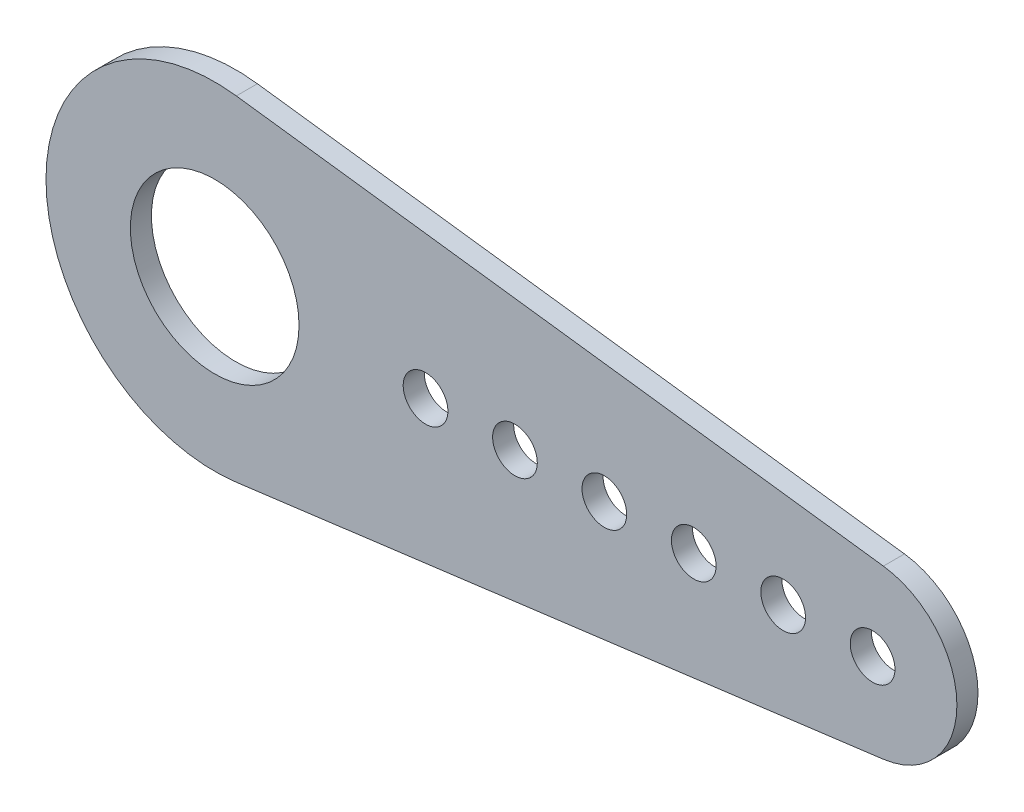
SolidWorks part; units mm, degrees
material "Custom Plastic"
ref_plane "X-Y Datum" through (0, 0, 0) normal (0, 0, 1) x (1, 0, 0)
ref_plane "X-Z Datum" through (0, 0, 0) normal (0, 1, 0) x (1, 0, 0)
ref_plane "Y-Z Datum" through (0, 0, 0) normal (1, 0, 0) x (0, 0, -1)
sketch "Flat sketch" plane through (0, 0, 0) normal (0, 0, 1) x (1, 0, 0)
  line L0 (-12.7, 0) -> (99.06, 0) construction
  line L1 (99.06, 0) -> (85.598, 0) construction
  line L2 (3.2564, 25.1904) -> (100.6882, 12.5952)
  line L3 (3.2564, -25.1904) -> (100.6882, -12.5952)
  line L4 (100.6882, 12.5952) -> (100.6882, -12.5952) construction
  circle A0 centre (0, 0) radius 12.7
  circle A1 centre (0, 0) radius 25.4
  circle A2 centre (99.06, 0) radius 3.3655
  circle A3 centre (85.598, 0) radius 3.3655
  circle A4 centre (72.136, 0) radius 3.3655
  circle A5 centre (58.674, 0) radius 3.3655
  circle A6 centre (45.212, 0) radius 3.3655
  circle A7 centre (31.75, 0) radius 3.3655
  circle A8 centre (99.06, 0) radius 12.7
  point P5 (12.7, 0)
  point P9 (25.4, 0)
  dimension "D1" = 25.4
  dimension "D2" = 50.8
  dimension "D3" = 6.731
  dimension "D7" = 25.4
  dimension "D5" = 13.462
  dimension "D6" = 6.35
  dimension "D4" = 6
extrude "Extrude face" add sketch "Flat sketch" along normal blind 3.175 contours A1 A0 | A8 L2 A1 L3 A3 A4 A5 A6 A7 | A7 | A6 | A5 | A4 | A8 A3 | A3 A8 | A8 A3 A2 | A2 region at (52.0564, 0, 0) region at (18.5375, 16.2954, 0) region at (108.3309, 8.1496, 0) region at (84.6426, 0, 0) region at (87.5186, 0, 0) region at (99.06, 0, 0) region at (72.136, 0, 0) region at (58.674, 0, 0) region at (45.212, 0, 0) region at (31.75, 0, 0)
extrude "Extrude cut - holes" cut sketch "Flat sketch<4>" along normal up to surface (3.175 mm away) contours A7 | A6 | A5 | A4 | A8 A3 | A2 | A3 A8 region at (84.6426, 0, 0) region at (87.5186, 0, 0) region at (99.06, 0, 0) region at (72.136, 0, 0) region at (58.674, 0, 0) region at (45.212, 0, 0) region at (31.75, 0, 0) up to face at (12.7, 0, 3.175)
sketch "Flat sketch<4>" plane through (0, 0, 0) normal (0, 0, 1) x (1, 0, 0) same geometry as "Flat sketch"
equation "\"Torsion Bar O.D.\"= 1in"
equation "\"Lever I.D. Torsion O.D. Clearance\"= 0"
equation "\"Lever I.D.\"= \"Torsion Bar O.D.\" + \"Lever I.D. Torsion O.D. Clearance\""
equation "\"D1@Flat sketch\" = \"Lever I.D.\""
equation "\"Lever O.D.\"= 2in"
equation "\"D2@Flat sketch\" = \"Lever O.D.\""
equation "\"Lever Rod end I.D.\" = 0.265"
equation "\"D3@Flat sketch\" = \"Lever Rod end I.D.\""
equation "\"Distance b/w Lever Rod end holes\"= 0"
equation "\"Number of Lever Rod end holes\" = 0"
equation "\"Lever arc radius\"= 0.5"
equation "\"Lever rod end hole and Lever O.D. clearance\"= 0.25"
equation "\"D6@Flat sketch\" = \"Lever rod end hole and Lever O.D. clearance\""
equation "\"Lever thickness\"= 1 / 8in"
equation "\"D1@Extrude face\" = \"Lever thickness\""
